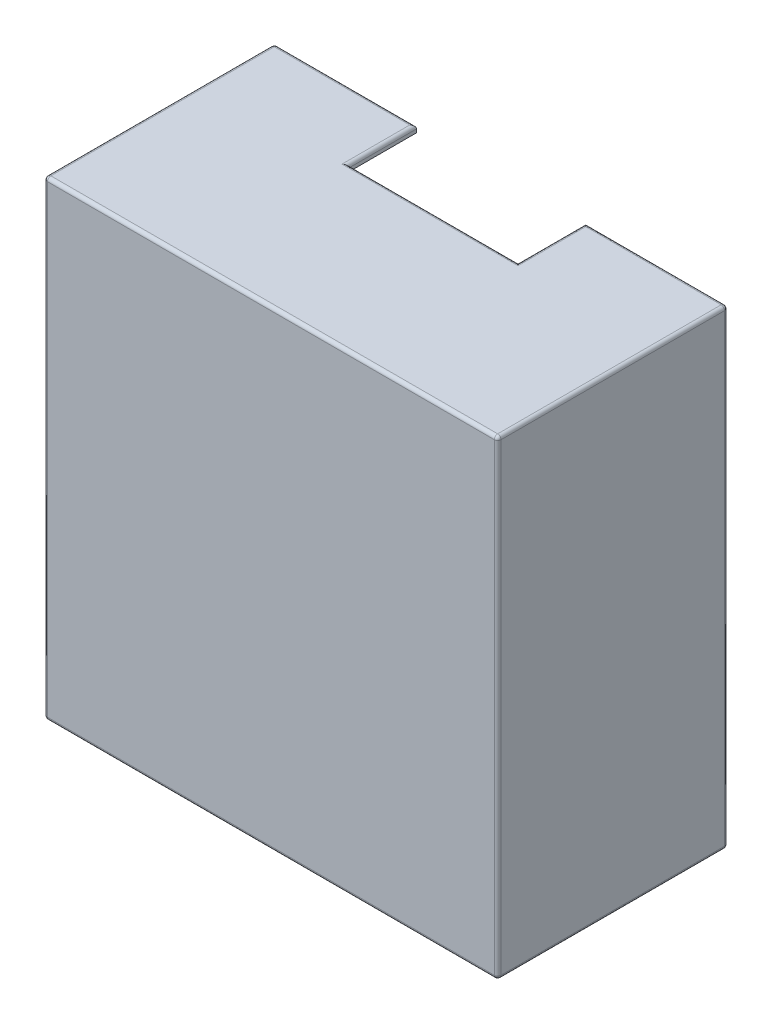
SolidWorks part; units mm, degrees
ref_plane "前视基准面" through (0, 0, 0) normal (0, 0, 1) x (1, 0, 0)
ref_plane "上视基准面" through (0, 0, 0) normal (0, 1, 0) x (1, 0, 0)
ref_plane "右视基准面" through (0, 0, 0) normal (1, 0, 0) x (0, 0, -1)
sketch "草图1" plane through (0, 0, 0) normal (0, 1, 0) x (1, 0, 0)
  line L1 (134, -68) -> (-134, -68)
  line L2 (134, -68) -> (134, 68)
  line L3 (134, 68) -> (-134, 68)
  line L4 (-134, -68) -> (-134, 68)
  line L5 (134, -68) -> (-134, 68) construction
  line L6 (134, 68) -> (-134, -68) construction
  point P0 (0, 0)
  dimension "D1" = 268
  dimension "D2" = 136
extrude "凸台-拉伸1" add sketch "草图1" along normal blind 278
sketch "草图2" plane through (0, 0, -68) normal (0, 0, -1) x (-1, 0, 0)
  line L14 (-130, 4) -> (130, 4)
  line L15 (130, 4) -> (130, 274)
  line L16 (130, 274) -> (-130, 274)
  line L17 (-130, 274) -> (-130, 4)
  line L18 (-130, 4) -> (130, 4)
  line L19 (130, 4) -> (130, 274)
  line L20 (130, 274) -> (-130, 274)
  line L21 (-130, 274) -> (-130, 4)
  dimension "D1" = 4
extrude "切除-拉伸1" cut sketch "草图2" against normal offset from surface (134 mm away) 2 up to face at (0, 139, 68)
sketch "草图3" plane through (0, 278, 0) normal (0, 1, 0) x (1, 0, 0)
  line L0 (0, 68) -> (0, -68) construction
  line L1 (134, 68) -> (-134, 68) construction
  line L2 (-134, -68) -> (134, -68) construction
  line L3 (50, 68) -> (-50, 68)
  line L4 (-50, 68) -> (-50, 28)
  line L5 (-50, 28) -> (50, 28)
  line L6 (50, 68) -> (50, 28)
  point P10 (0, 28)
  dimension "D1" = 40
  dimension "D2" = 100
extrude "切除-拉伸2" cut sketch "草图3" against normal up to next
sketch "草图4" plane through (0, 0, 0) normal (0, -1, 0) x (1, 0, 0)
  line L0 (0, 68) -> (0, -68) construction
  line L1 (-134, 68) -> (134, 68) construction
  line L2 (134, -68) -> (-134, -68) construction
  line L3 (-134, 0) -> (134, 0) construction
  line L4 (-134, -68) -> (-134, 68) construction
  line L5 (134, 68) -> (134, -68) construction
  line L6 (-134, 40) -> (-134, 44)
  line L7 (-134, 44) -> (-133, 44)
  line L8 (-133, 44) -> (-133, 40)
  line L9 (-133, 40) -> (-134, 40)
  line L10 (-133, -40) -> (-134, -40)
  line L11 (-133, -44) -> (-133, -40)
  line L12 (-134, -44) -> (-133, -44)
  line L13 (-134, -40) -> (-134, -44)
  line L14 (134, -40) -> (134, -44)
  line L15 (134, -44) -> (133, -44)
  line L16 (133, -44) -> (133, -40)
  line L17 (133, -40) -> (134, -40)
  line L18 (133, 40) -> (134, 40)
  line L19 (133, 44) -> (133, 40)
  line L20 (134, 44) -> (133, 44)
  line L21 (134, 40) -> (134, 44)
  dimension "D1" = 1
  dimension "D2" = 4
  dimension "D3" = 40
fillet "圆角1" radius 2 17 edges at (134, 278, 0) (134, 0, 0) (-134, 0, 0) (-134, 278, 0) (0, 0, -68) (134, 139, -68) (92, 278, -68) (50, 278, -48) (0, 278, -28) (-50, 278, -48) (-92, 278, -68) (-134, 139, -68) (0, 0, 68) (134, 139, 68) (0, 278, 68) (-130, 139, 66) (-134, 139, 68)
